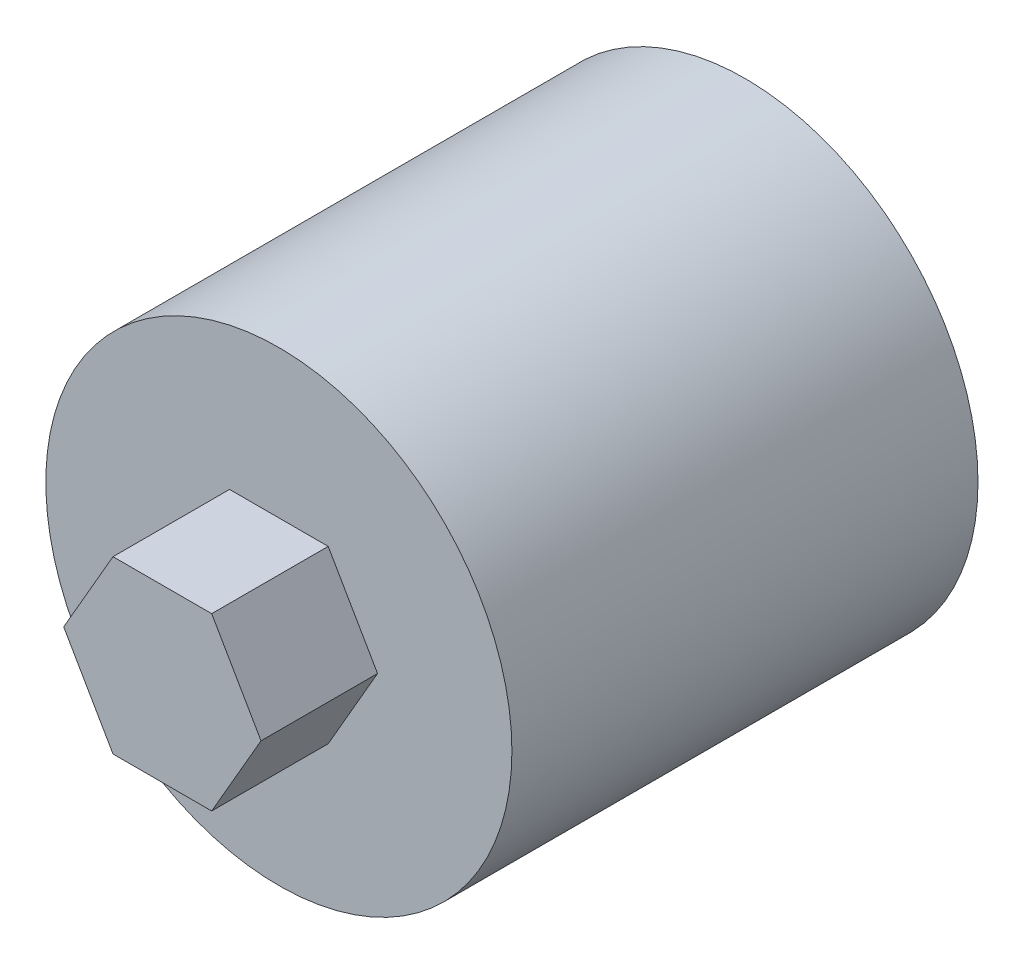
SolidWorks part; units mm, degrees
ref_plane "前视基准面" through (0, 0, 0) normal (0, 0, 1) x (1, 0, 0)
ref_plane "上视基准面" through (0, 0, 0) normal (0, 1, 0) x (1, 0, 0)
ref_plane "右视基准面" through (0, 0, 0) normal (1, 0, 0) x (0, 0, -1)
other "Configuration Table"
sketch "草图1" plane through (0, 0, 0) normal (0, 0, 1) x (1, 0, 0)
  line L0 (0, 0) -> (1.7387, 0.4659) construction
  line L1 (0, 0) -> (1.6291, 0.4551)
  line L2 (0, 0) -> (1.6291, -0.4551)
  line L3 (0, 0) -> (1.7387, -0.4659) construction
  line L4 (0, 0) -> (2.425, 0) construction
  line L5 (1.7387, 0.4659) -> (1.7387, -0.4659) construction
  circle A0 centre (0, 0) radius 1.525
  circle A1 centre (0, 0) radius 2.425
  circle A2 centre (0, 0) radius 1.6914 construction
  circle A3 centre (0, 0) radius 1.8 construction
  circle A4 centre (0, 0) radius 3
  spline S0 degree 4 poles (1.6291, 0.4551) (1.6415, 0.4586) (1.6769, 0.4656) (1.746, 0.4684) (1.8576, 0.4574) (1.9985, 0.4209) (2.171, 0.3489) (2.3582, 0.2351) (2.5438, 0.0819) (2.7191, -0.1093) (2.8693, -0.3205) (2.9946, -0.5472) (3.1006, -0.7975) (3.1986, -1.1195) (3.2658, -1.5159) (3.2754, -1.9832) (3.2064, -2.4974) (3.0631, -2.9965) (2.8558, -3.471) (2.5865, -3.9159) (2.2706, -4.3232) (1.901, -4.6937) (1.507, -5.0164) (1.0559, -5.3028) (0.6986, -5.4883) (0.2793, -5.6591) (0.0342, -5.7399) (-0.2484, -5.8241) (-0.3932, -5.8525) (-0.5197, -5.8826) (-0.5587, -5.8884) (-0.5863, -5.894) (-0.6011, -5.8971) knots 0 0 0 0 0 0.005604 0.015718 0.02996 0.048734 0.068727 0.096889 0.125051 0.153212 0.181374 0.209535 0.237696 0.271429 0.327752 0.384075 0.440398 0.496721 0.553044 0.609367 0.66569 0.722013 0.778336 0.834659 0.890982 0.909091 0.954545 0.977273 0.988636 0.994318 1 1 1 1 1 construction
  spline S1 degree 4 poles (1.6291, 0.4551) (1.6415, 0.4586) (1.6769, 0.4656) (1.746, 0.4684) (1.8576, 0.4574) (1.9985, 0.4209) (2.171, 0.3489) (2.3582, 0.2351) (2.5438, 0.0819) (2.7191, -0.1093) (2.8693, -0.3205) (2.9946, -0.5472) (3.1006, -0.7975) (3.1986, -1.1195) (3.2658, -1.5159) (3.2754, -1.9832) (3.2064, -2.4974) (3.0631, -2.9965) (2.8558, -3.471) (2.5865, -3.9159) (2.2706, -4.3232) (1.901, -4.6937) (1.507, -5.0164) (1.0559, -5.3028) (0.6986, -5.4883) (0.3874, -5.615) (0.2408, -5.6686) (0.2052, -5.6811) knots 0 0 0 0 0 0.005604 0.015718 0.02996 0.048734 0.068727 0.096889 0.125051 0.153212 0.181374 0.209535 0.237696 0.271429 0.327752 0.384075 0.440398 0.496721 0.553044 0.609367 0.66569 0.722013 0.778336 0.834659 0.890982 0.909091 0.909091 0.909091 0.909091 0.909091
  spline S2 degree 4 poles (1.6291, -0.4551) (1.6415, -0.4586) (1.6769, -0.4656) (1.746, -0.4684) (1.8576, -0.4574) (1.9985, -0.4209) (2.171, -0.3489) (2.3582, -0.2351) (2.5438, -0.0819) (2.7191, 0.1093) (2.8693, 0.3205) (2.9946, 0.5472) (3.1006, 0.7975) (3.1986, 1.1195) (3.2658, 1.5159) (3.2754, 1.9832) (3.2064, 2.4974) (3.0631, 2.9965) (2.8558, 3.471) (2.5865, 3.9159) (2.2706, 4.3232) (1.901, 4.6937) (1.507, 5.0164) (1.0559, 5.3028) (0.6986, 5.4883) (0.2793, 5.6591) (0.0342, 5.7399) (-0.2484, 5.8241) (-0.3932, 5.8525) (-0.5197, 5.8826) (-0.5587, 5.8884) (-0.5863, 5.894) (-0.6011, 5.8971) knots 0 0 0 0 0 0.005604 0.015718 0.02996 0.048734 0.068727 0.096889 0.125051 0.153212 0.181374 0.209535 0.237696 0.271429 0.327752 0.384075 0.440398 0.496721 0.553044 0.609367 0.66569 0.722013 0.778336 0.834659 0.890982 0.909091 0.954545 0.977273 0.988636 0.994318 1 1 1 1 1 construction
  spline S3 degree 4 poles (1.6291, -0.4551) (1.6415, -0.4586) (1.6769, -0.4656) (1.746, -0.4684) (1.8576, -0.4574) (1.9985, -0.4209) (2.171, -0.3489) (2.3582, -0.2351) (2.5438, -0.0819) (2.7191, 0.1093) (2.8693, 0.3205) (2.9946, 0.5472) (3.1006, 0.7975) (3.1986, 1.1195) (3.2658, 1.5159) (3.2754, 1.9832) (3.2064, 2.4974) (3.0631, 2.9965) (2.8558, 3.471) (2.5865, 3.9159) (2.2706, 4.3232) (1.901, 4.6937) (1.507, 5.0164) (1.0559, 5.3028) (0.6986, 5.4883) (0.3874, 5.615) (0.2408, 5.6686) (0.2052, 5.6811) knots 0 0 0 0 0 0.005604 0.015718 0.02996 0.048734 0.068727 0.096889 0.125051 0.153212 0.181374 0.209535 0.237696 0.271429 0.327752 0.384075 0.440398 0.496721 0.553044 0.609367 0.66569 0.722013 0.778336 0.834659 0.890982 0.909091 0.909091 0.909091 0.909091 0.909091
  point P16 (1.7387, 0)
  dimension "内啮合齿顶圆直径" = 3.05
  dimension "内啮合分度圆直径" = 3.6
  dimension "内啮合基圆直径" = 3.3829
  dimension "内啮合齿根圆直径" = 4.85
  dimension "外径" = 6
  dimension "渐开线镜像线夹角" = 15
extrude "凸台-拉伸1" add sketch "草图1" along normal blind 5 contours A4 | A0
extrude "切除-拉伸2" cut sketch "草图1<3>" along normal through all contours A0 S3 A1 S1 region at (1.9135, 0, 0)
sketch "草图1<3>" plane through (0, 0, 0) normal (0, 0, 1) x (1, 0, 0) same geometry as "草图1"
pattern_circular "阵列(圆周)1" count 9 over 360 about axis through (0, 0, 5) along (0, 0, 1) of "切除-拉伸2"
sketch "草图2" plane through (0, 0, 5) normal (0, 0, 1) x (1, 0, 0)
  line L1 (0.6351, 1.1) -> (-0.6351, 1.1)
  line L2 (-0.6351, 1.1) -> (-1.2702, 0)
  line L3 (-1.2702, 0) -> (-0.6351, -1.1)
  line L4 (-0.6351, -1.1) -> (0.6351, -1.1)
  line L5 (0.6351, -1.1) -> (1.2702, 0)
  line L6 (1.2702, 0) -> (0.6351, 1.1)
  circle A0 centre (0, 0) radius 3
  circle A1 centre (0, 0) radius 3 construction
  circle A2 centre (0, 0) radius 1.2702
  circle A3 centre (0, 0) radius 1.1 construction
  dimension "D1" = 2.2
extrude "凸台-拉伸2" add sketch "草图2" along normal blind 1 contours A0
extrude "凸台-拉伸3" add sketch "草图2<3>" along normal blind 1.5 from surface contours L1 L2 L3 L4 L5 L6 starting at face at (3, 0, 6)
sketch "草图2<3>" plane through (0, 0, 5) normal (0, 0, 1) x (1, 0, 0) same geometry as "草图2"
equation "\"m\"= 0.4'模数"
equation "\"z1\"= 6'外啮合齿轮数"
equation "\"a\"= 20度'压力角"
equation "\"z2\"= 9'内啮合齿轮数"
equation "\"hax\"= 1'齿顶高系数"
equation "\"cx\"= 0.25'顶隙系数"
equation "\"ha\"= \"hax\" * \"m\"'齿顶高"
equation "\"hf\"= ( \"hax\" + \"cx\" ) * \"m\"'齿根高"
equation "\"d1\"= \"m\" * \"z1\"'外啮合分度圆直径"
equation "\"da1\"= ( \"z1\" + 2 ) * \"m\"'外啮合齿顶圆直径"
equation "\"df1\"= \"d1\" - 2 * \"hf\"'外啮合齿根圆直径"
equation "\"db1\"= \"d1\" * cos ( \"a\" )'外啮合基圆直径"
equation "\"p\"= \"m\" * PI'齿距"
equation "\"d2\"= \"m\" * \"z2\"'内啮合分度圆直径"
equation "\"db2\"= \"d2\" * cos ( \"a\" )'内啮合基圆直径"
equation "\"da2\"= ( \"z2\" - 2 ) * \"m\"'内啮合齿顶圆直径"
equation "\"df2\"= \"d2\" + 2 * \"hf\"'内啮合齿根圆直径"
equation "\"内啮合齿顶圆直径@草图1\" = \"da2\" + 0.5 * \"hf\""
equation "\"内啮合齿根圆直径@草图1\"= \"df2\" + 0.5 * \"hf\""
equation "\"内啮合分度圆直径@草图1\"= \"d2\""
equation "\"内啮合基圆直径@草图1\"= \"db2\""
equation "\"渐开线镜像线夹角@草图1\"= 360度 / 4 / \"z2\" + 360度 / 4 / \"z2\" / 2"
equation "\"do\"= IIF ( \"edo\" >= ( \"df2\" + 1 ) , \"edo\" , ( \"df2\" + 1 ) )'外圈直径"
equation "\"h\"= 5'厚度"
equation "\"外径@草图1\"= \"do\""
equation "\"厚度@凸台-拉伸1\"= \"h\""
equation "\"内啮合齿轮数@阵列(圆周)1\"= \"z2\""
equation "\"edo\"= 6'期望的外圈直径"
